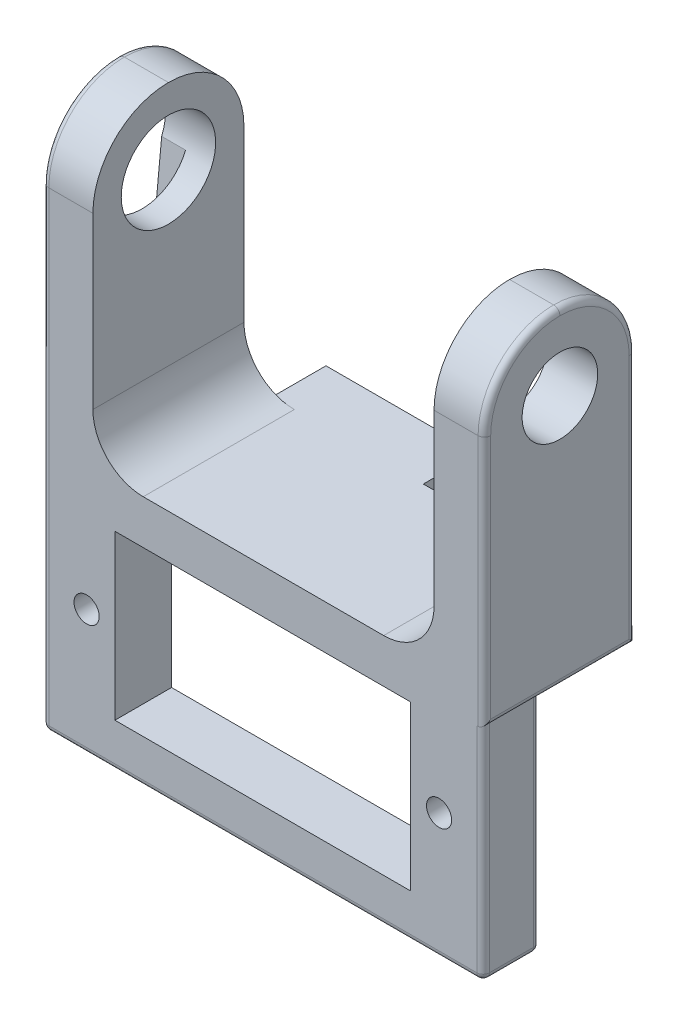
SolidWorks part; units mm, degrees
ref_plane "Front Plane" through (0, 0, 0) normal (0, 0, 1) x (1, 0, 0)
ref_plane "Top Plane" through (0, 0, 0) normal (0, 1, 0) x (1, 0, 0)
ref_plane "Right Plane" through (0, 0, 0) normal (1, 0, 0) x (0, 0, -1)
sketch "Sketch2" plane through (0, 0, 0) normal (0, 0, 1) x (1, 0, 0)
  line L0 (0, 0) -> (0, 43.5)
  line L1 (0, 0) -> (35, 0)
  line L4 (5.75, 3.5) -> (29.25, 3.5)
  line L5 (5.75, 3.5) -> (5.75, 16.5)
  line L6 (5.75, 16.5) -> (29.25, 16.5)
  line L7 (29.25, 16.5) -> (29.25, 3.5)
  line L8 (17.5, 16.5) -> (17.5, 3.5) construction
  line L9 (35, 0) -> (35, 17.5)
  line L10 (35, 17.5) -> (35.1, 17.5)
  line L11 (35.1, 17.5) -> (35.1, 43.5)
  line L13 (0, 43.5) -> (4, 43.5)
  line L14 (4, 43.5) -> (4, 24)
  line L15 (35.1, 43.5) -> (31.1, 43.5)
  line L16 (31.1, 43.5) -> (31.1, 24)
  line L18 (8, 20) -> (27.1, 20)
  circle A0 centre (3.5, 10) radius 1
  circle A1 centre (31.5, 10) radius 1
  arc A2 (8, 20) -> (4, 24) centre (8, 24) cw
  arc A3 (27.1, 20) -> (31.1, 24) centre (27.1, 24) ccw
  dimension "D8" = 2
  dimension "D1" = 43.5
  dimension "D2" = 35
  dimension "D3" = 23.5
  dimension "D4" = 13
  dimension "D5" = 3.5
  dimension "D6" = 5.75
  dimension "D7" = 2.25
  dimension "D9" = 6.5
  dimension "D10" = 17.5
  dimension "D11" = 0.1
  dimension "D12" = 19.5
  dimension "D13" = 4
  dimension "D14" = 19.1
  dimension "D15" = 2.15
  dimension "D16" = 3.5
extrude "Boss-Extrude1" add sketch "Sketch2" along normal blind 16.2658
sketch "Sketch4" plane through (0, 0, 0) normal (0, 0, -1) x (-1, 0, 0)
  line L0 (0, 0) -> (0, 17.5)
  line L1 (0, 43.5) -> (0, 0) construction
  line L2 (0, 17.5) -> (-6.25, 17.5)
  line L3 (-6.25, 17.5) -> (-6.25, 16.5)
  line L4 (-6.25, 16.5) -> (-18.25, 16.5)
  line L5 (-29.25, 16.5) -> (-5.75, 16.5) construction
  line L6 (-18.25, 16.5) -> (-18.25, 17.5)
  line L7 (-18.25, 17.5) -> (-35.25, 17.5)
  line L8 (-35.25, 17.5) -> (-35.25, 0)
  line L9 (-35.25, 0) -> (0, 0)
  dimension "D1" = 17.5
  dimension "D2" = 6.25
  dimension "D3" = 1
  dimension "D4" = 12
  dimension "D5" = 17
  dimension "D6" = 17.5
extrude "Cut-Extrude1" cut sketch "Sketch4" against normal blind 11.7658
sketch "Sketch5" plane through (0, 0, 0) normal (0, 0, -1) x (-1, 0, 0)
  line L0 (0, 17.5) -> (-6.25, 17.5)
  line L1 (-6.25, 17.5) -> (-6.25, 20)
  line L2 (-6.25, 20) -> (-18.25, 20)
  line L3 (-27.1, 20) -> (-8, 20) construction
  line L4 (-18.25, 20) -> (-18.25, 17.5)
  line L5 (-18.25, 17.5) -> (-35.1, 17.5)
  line L6 (-35.1, 17.5) -> (-35.1, 43.5)
  line L7 (-35.1, 43.5) -> (0, 43.5)
  line L8 (0, 43.5) -> (0, 17.5)
extrude "Cut-Extrude2" cut sketch "Sketch5" against normal blind 4.2658
sketch "Sketch6" plane through (0, 0, 0) normal (0, 0, -1) x (-1, 0, 0)
  line L0 (-15.25, 18.25) -> (-9.25, 18.25) construction
  line L1 (-18.25, 17.5) -> (-18.25, 20) construction
  line L2 (-6.25, 20) -> (-6.25, 16.5) construction
  line L3 (-18.25, 16.5) -> (-6.25, 16.5) construction
  circle A0 centre (-15.25, 18.25) radius 0.8
  circle A1 centre (-9.25, 18.25) radius 0.8
  dimension "D1" = 1.6
  dimension "D4" = 3
  dimension "D5" = 1.75
  dimension "D2" = 6
  dimension "D3" = 3
extrude "Cut-Extrude3" cut sketch "Sketch6" against normal blind 3
sketch "Sketch7" plane through (35.1, 0, 0) normal (1, 0, 0) x (0, 0, -1)
  line L0 (-16.2658, 17.5) -> (-16.2658, 43.5) construction
  line L2 (-16.2658, 43.5) -> (-4.2658, 43.5) construction
  circle A0 centre (-10.2658, 37.5) radius 3
  dimension "D1" = 6
  dimension "D2" = 6
  dimension "D3" = 6
extrude "Cut-Extrude4" cut sketch "Sketch7" against normal up to next
sketch "Sketch8" plane through (0, 0, 0) normal (-1, 0, 0) x (0, 0, 1)
  line L0 (16.2658, 43.5) -> (4.2658, 43.5) construction
  line L1 (4.2658, 17.5) -> (4.2658, 43.5) construction
  circle A0 centre (10.2658, 37.5) radius 3.75
  dimension "D2" = 7.5
  dimension "D1" = 6
  dimension "D3" = 6
extrude "Cut-Extrude5" cut sketch "Sketch8" against normal up to next
sketch "Sketch9" plane through (0, 0, 0) normal (-1, 0, 0) x (0, 0, 1)
  line L0 (6.8012, 36.0649) -> (8.2658, 21.5)
  line L1 (4.2658, 17.5) -> (4.2658, 43.5) construction
  line L2 (16.2658, 43.5) -> (4.2658, 43.5) construction
  line L3 (10.2658, 41.25) -> (10.2658, 33.75) construction
  line L4 (13.7303, 36.0649) -> (12.2658, 21.5)
  circle A0 centre (10.2658, 37.5) radius 3.75 construction
  arc A1 (8.2658, 21.5) -> (12.2658, 21.5) centre (10.2658, 21.7011) ccw
  arc A2 (6.8012, 36.0649) -> (13.7303, 36.0649) centre (10.2658, 37.5) ccw
  dimension "D1" = 2.5354
  dimension "D2" = 7.4351
  dimension "D3" = 14.5649
  dimension "D4" = 1.4646
extrude "Cut-Extrude6" cut sketch "Sketch9" against normal blind 1.9
fillet "Fillet1" radius 6 2 edges at (2, 43.5, 4.2658) (2, 43.5, 16.2658)
fillet "Fillet2" radius 6 2 edges at (33.1, 43.5, 16.2658) (33.1, 43.5, 4.2658)
fillet "Fillet3" radius 0.5 14 edges at (0, 27.5, 4.2658) (0, 41.7426, 6.0231) (0, 41.7426, 14.5084) (3.125, 17.5, 4.2658) (3.125, 17.5, 11.7658) (0, 17.5, 8.0158) (0, 8.75, 11.7658) (0, 0, 14.0158) (0, 18.75, 16.2658) (17.5, 0, 16.2658) (35, 8.75, 16.2658) (17.5, 0, 11.7658) (35, 8.75, 11.7658) (35, 0, 14.0158)
fillet "Fillet4" radius 0.5 5 edges at (35.1, 27.5, 4.2658) (35.1, 27.5, 16.2658) (35.1, 41.7426, 14.5084) (35.1, 41.7426, 6.0231) (35.1, 17.5, 10.2658)
